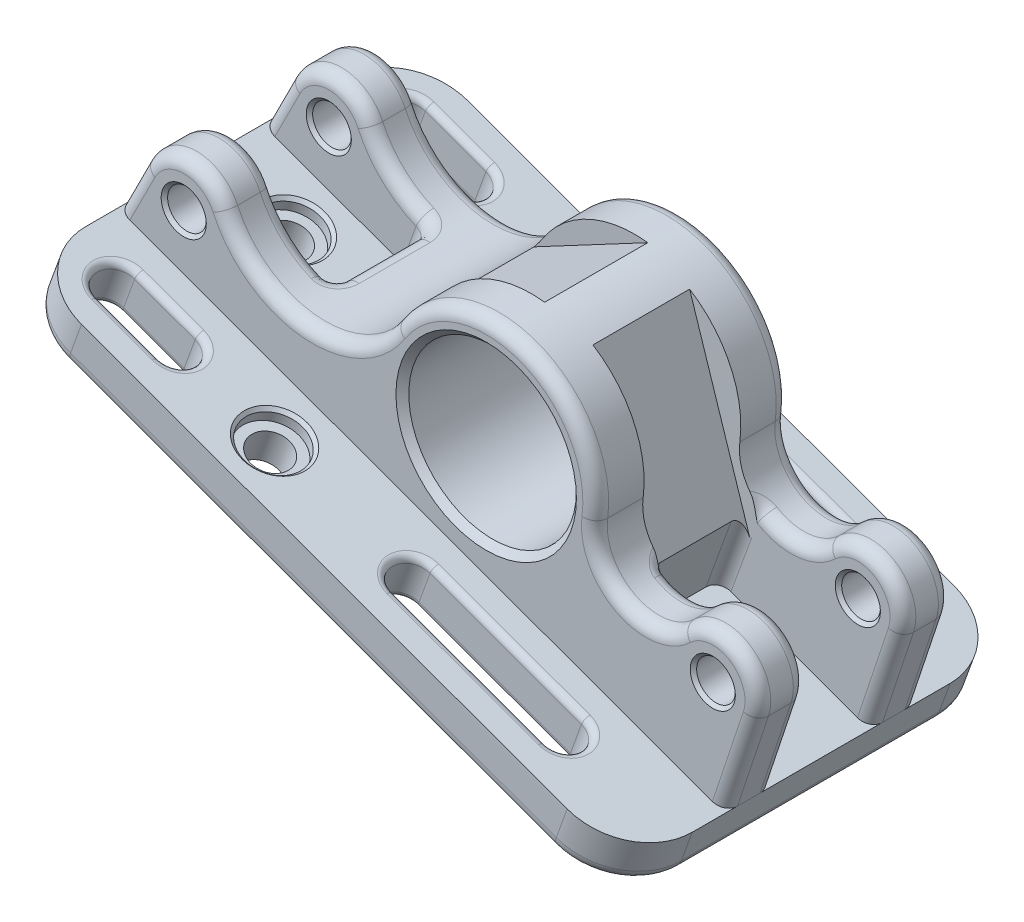
SolidWorks part; units mm, degrees
material "7075-T6, Plate (SS)"
ref_plane "Front Plane" through (0, 0, 0) normal (0, 0, 1) x (1, 0, 0)
ref_plane "Top Plane" through (0, 0, 0) normal (0, 1, 0) x (1, 0, 0)
ref_plane "Right Plane" through (0, 0, 0) normal (1, 0, 0) x (0, 0, -1)
sketch "Sketch1" plane through (0, 0, 0) normal (0, 0, 1) x (1, 0, 0)
  line L1 (2.9256, 48.9181) -> (97.0713, 14.6519)
  line L2 (97.0713, 14.6519) -> (109.144, 47.8213) construction
  line L3 (2.9256, 48.9181) -> (16.6344, 86.5828) construction
  line L4 (64.2, 56.8) -> (64.2, 145) construction
  line L5 (17.2835, 64.9758) -> (54.2, 106.8)
  line L6 (74.2, 121.8) -> (101.5245, 50.2773)
  line L7 (40.7, 148) -> (40.7, 52.5253) construction
  line L8 (87.7, 148) -> (87.7, 56.8) construction
  arc A1 (97.0713, 14.6519) -> (108.8436, 11.9213) centre (114.1723, 61.6365) ccw
  circle A2 centre (17.2835, 64.9758) radius 3
  circle A3 centre (101.5245, 50.2773) radius 3
  circle A8 centre (74.2, 121.8) radius 3
  circle A9 centre (54.2, 106.8) radius 3
  spline S1 degree 3 poles (108.8436, 11.9213) (110.0019, 11.7972) (111.159, 11.6604) (114.5227, 11.2279) (116.7249, 10.9021) (123.3121, 9.8294) (127.6782, 8.9871) (140.7169, 6.3137) (149.3307, 4.3374) (166.474, 1.206) (175.0008, 0.0515) (187.7816, -0.2014) (192.0406, -0.0398) (200.5758, 0.9156) (204.8521, 1.7093) (209.1515, 2.8921) knots 0.514918 0.514918 0.514918 0.514918 0.53125 0.53125 0.5625 0.5625 0.625 0.625 0.75 0.75 0.875 0.875 0.9375 0.9375 1 1 1 1
  point P0 (64.2, 56.8)
  point P18 (17.2835, 64.9758)
  point P19 (101.5245, 50.2773)
  point P26 (74.2, 121.8)
  point P27 (54.2, 106.8)
  dimension "D11" = 6
  dimension "D12" = 6
  dimension "D15" = 46.9165
  dimension "D17" = 6
  dimension "D18" = 6
  dimension "D3" = 20
  dimension "D4" = 35
  dimension "D5" = 8
  dimension "D6" = 10
  dimension "D7" = 8
  dimension "D8" = 10
  dimension "D9" = 65
  dimension "D10" = 50
  dimension "D13" = 37.3245
  dimension "D14" = 6.5227
  dimension "D16" = 8.1758
sketch "Sketch4" plane through (0, 0, 0) normal (0, 0, 1) x (1, 0, 0)
  line L0 (7.0298, 60.1945) -> (4.6357, 53.6166)
  line L1 (4.6357, 53.6166) -> (98.7814, 19.3504)
  line L2 (7.0298, 60.1945) -> (101.1755, 25.9282)
  line L3 (2.9256, 48.9181) -> (16.6344, 86.5828) construction
  line L4 (97.0713, 14.6519) -> (109.144, 47.8213) construction
  line L5 (101.1755, 25.9282) -> (98.7814, 19.3504)
  dimension "D1" = 7
extrude "Boss-Extrude2" add sketch "Sketch4" along normal blind 30 and the other way blind 30 separate body
sketch "Sketch5" plane through (0, 0, 0) normal (0, 0, 1) x (1, 0, 0)
  line L0 (101.1755, 25.9282) -> (105.9964, 40.4548)
  line L1 (7.0298, 60.1945) -> (11.0338, 68.1294)
  line L5 (101.1755, 25.9282) -> (7.0298, 60.1945)
  line L8 (17.2835, 64.9758) -> (6.1272, 34.324) construction
  line L10 (101.1755, 25.9282) -> (7.0298, 60.1945) construction
  line L12 (7.0298, 60.1945) -> (4.6357, 53.6166) construction
  arc A0 (81.0509, 54.5531) -> (49.9057, 66.0017) centre (64.2, 56.8) ccw
  arc A1 (105.9964, 40.4548) -> (94.5124, 47.7165) centre (99.3527, 42.6596) ccw
  arc A2 (23.6504, 67.8857) -> (11.0338, 68.1294) centre (17.2835, 64.9758) ccw
  circle A3 centre (64.2, 56.8) radius 13
  circle A4 centre (99.3527, 42.6596) radius 3
  circle A5 centre (17.2835, 64.9758) radius 3
  arc A6 (23.6504, 67.8857) -> (49.9057, 66.0017) centre (37.293, 74.1209) ccw
  arc A7 (81.0509, 54.5531) -> (94.5124, 47.7165) centre (88.9807, 53.4957) ccw
  point P18 (16.5995, 63.0965)
  point P22 (17.2835, 64.9758)
  dimension "D1" = 14.0006
  dimension "D2" = 4
  dimension "D3" = 14
  dimension "D8" = 26
  dimension "D9" = 6
  dimension "D5" = 6
  dimension "D6" = 2
extrude "Boss-Extrude5" add sketch "Sketch5" along normal blind 15 and the other way blind 15 contours L5 A3 A4 A5 region at (54.4798, 44.0974, 0)
sketch "Sketch6" plane through (20.1685, 55.4124, 0) normal (0.342, 0.9397, 0) x (0.9397, -0.342, 0)
  line L1 (-13.9818, -7.5) -> (10.9889, -7.5)
  line L2 (61.3272, -7.5) -> (95.1205, -7.5)
  line L3 (-13.9818, 7.5) -> (10.9889, 7.5)
  line L4 (95.1205, -7.5) -> (95.1205, 7.5)
  line L6 (-13.9818, 30) -> (-13.9818, -30) construction
  line L7 (61.3272, 7.5) -> (61.3272, -7.5)
  line L8 (10.9889, 7.5) -> (10.9889, -7.5)
  line L9 (-13.9818, 7.5) -> (-13.9818, -7.5)
  line L10 (61.3272, 7.5) -> (95.1205, 7.5)
  point P0 (0, 0)
  dimension "D1" = 15
extrude "Cut-Extrude1" cut sketch "Sketch6" along normal blind 41
chamfer "Chamfer1" distance 1 angle 45 2 edges at (77.2, 56.8, -15) (77.2, 56.8, 15)
sketch "Sketch8" plane through (20.1685, 55.4124, 0) normal (0.342, 0.9397, 0) x (0.9397, -0.342, 0)
  line L0 (40.9015, 0) -> (-1.0985, 0) construction
  line L1 (19.9015, 0) -> (19.9015, 22.5) construction
  line L2 (27.9015, -14) -> (53.9015, -14) construction
  line L3 (27.9015, -14) -> (53.9015, -14)
  line L4 (40.9015, -14) -> (40.9015, 14) construction
  circle A0 centre (-1.0985, 0) radius 3
  circle A1 centre (19.9015, 22.5) radius 3
  circle A2 centre (19.9015, -22.5) radius 3
  dimension "D2" = 6
  dimension "D3" = 6
  dimension "D4" = 6
  dimension "D1" = 42
  dimension "D5" = 22.5
extrude "Cut-Extrude3" cut sketch "Sketch8" against normal blind 10 contours A2 | A0 | A1 region at (19.1362, 55.7881, 0) region at (38.8698, 48.6057, -22.5) region at (38.8698, 48.6057, 22.5)
chamfer "Chamfer3" distance 0.5 angle 45 8 edges at (102.3527, 42.6596, -7.5) (102.3527, 42.6596, -15) (96.3527, 42.6596, 7.5) (102.3527, 42.6596, 15) (14.2835, 64.9758, 7.5) (20.2835, 64.9758, 15) (20.2835, 64.9758, -7.5) (20.2835, 64.9758, -15)
sketch "Sketch9" plane through (20.1685, 55.4124, 0) normal (0.342, 0.9397, 0) x (0.9397, -0.342, 0)
  circle A0 centre (19.9015, -22.5) radius 3 construction
  circle A1 centre (-1.0985, 0) radius 3 construction
  circle A2 centre (19.9015, 22.5) radius 3 construction
  circle A3 centre (19.9015, -22.5) radius 3
  circle A4 centre (-1.0985, 0) radius 3
  circle A5 centre (19.9015, 22.5) radius 3
  circle A6 centre (19.9015, -22.5) radius 4.5
  circle A7 centre (-1.0985, 0) radius 4.5
  circle A8 centre (19.9015, 22.5) radius 4.5
  dimension "D1" = 1.5
extrude "Cut-Extrude4" cut sketch "Sketch9" against normal blind 2
chamfer "Chamfer5" distance 0.5 angle 45 1 edges at (34.6412, 50.1448, 22.5)
chamfer "Chamfer6" distance 0.5 angle 45 2 edges at (14.9076, 57.3272, 0) (34.6412, 50.1448, -22.5)
sketch "Sketch10" plane through (20.1685, 55.4124, 0) normal (0.342, 0.9397, 0) x (0.9397, -0.342, 0)
  line L0 (-13.9818, 22.5) -> (86.2059, 22.5) construction
  line L1 (86.2059, 30) -> (86.2059, 15) construction
  line L2 (42.7393, 25.5) -> (42.7393, 19.5) construction
  line L3 (42.7393, 19.5) -> (67.7393, 19.5)
  line L4 (67.7393, 25.5) -> (67.7393, 19.5) construction
  line L5 (42.7393, 25.5) -> (67.7393, 25.5)
  line L7 (42.7393, 19.5) -> (67.7393, 25.5) construction
  line L8 (42.7393, 25.5) -> (67.7393, 19.5) construction
  line L9 (-5.974, 25.552) -> (-5.974, 19.552) construction
  line L10 (-5.974, 19.552) -> (4.026, 19.552)
  line L11 (4.026, 25.552) -> (4.026, 19.552) construction
  line L12 (-5.974, 25.552) -> (4.026, 25.552)
  line L13 (-5.974, 19.552) -> (4.026, 25.552) construction
  line L14 (-5.974, 25.552) -> (4.026, 19.552) construction
  line L15 (-1.0985, 0) -> (63.2348, 0) construction
  line L16 (-5.974, -25.552) -> (4.026, -19.552) construction
  line L17 (-5.974, -19.552) -> (4.026, -25.552) construction
  line L18 (4.026, -25.552) -> (4.026, -19.552) construction
  line L19 (-5.974, -25.552) -> (-5.974, -19.552) construction
  line L20 (42.7393, -25.5) -> (67.7393, -19.5) construction
  line L21 (42.7393, -19.5) -> (67.7393, -25.5) construction
  line L22 (67.7393, -25.5) -> (67.7393, -19.5) construction
  line L23 (42.7393, -25.5) -> (42.7393, -19.5) construction
  line L24 (-5.974, -25.552) -> (4.026, -25.552)
  line L25 (-5.974, -19.552) -> (4.026, -19.552)
  line L26 (42.7393, -25.5) -> (67.7393, -25.5)
  line L27 (42.7393, -19.5) -> (67.7393, -19.5)
  arc A0 (42.7393, 25.5) -> (42.7393, 19.5) centre (42.7393, 22.5) ccw
  arc A1 (67.7393, 25.5) -> (67.7393, 19.5) centre (67.7393, 22.5) cw
  arc A3 (-5.974, 25.552) -> (-5.974, 19.552) centre (-5.974, 22.552) ccw
  arc A4 (4.026, 25.552) -> (4.026, 19.552) centre (4.026, 22.552) cw
  arc A5 (4.026, -25.552) -> (4.026, -19.552) centre (4.026, -22.552) ccw
  arc A6 (-5.974, -25.552) -> (-5.974, -19.552) centre (-5.974, -22.552) cw
  arc A7 (67.7393, -25.5) -> (67.7393, -19.5) centre (67.7393, -22.5) ccw
  arc A8 (42.7393, -25.5) -> (42.7393, -19.5) centre (42.7393, -22.5) cw
  point P5 (55.2393, 22.5)
  point P11 (-0.974, 22.552)
  point P20 (19.9015, 22.5)
  point P36 (19.9015, -22.5)
  point P37 (-0.974, -22.552)
  point P38 (55.2393, -22.5)
  dimension "D2" = 3
  dimension "D3" = 3
  dimension "D1" = 6
  dimension "D4" = 25
  dimension "D5" = 6
  dimension "D6" = 10
extrude "Cut-Extrude5" cut sketch "Sketch10" against normal through all
fillet "Fillet5" radius 10 4 edges at (99.9785, 22.6393, -30) (99.9785, 22.6393, 30) (5.8328, 56.9055, 30) (5.8328, 56.9055, -30)
sketch "Sketch11" plane through (0, 0, -7.5) normal (0, 0, 1) x (1, 0, 0)
  line L0 (82.1122, 36.0592) -> (97.973, 30.2864)
  line L1 (77.7972, 34.4372) -> (101.1755, 25.9282)
  line L2 (82.1122, 36.0592) -> (83.8223, 40.7577)
  line L3 (97.973, 30.2864) -> (99.6831, 34.9849)
  line L4 (99.6831, 34.9849) -> (83.8223, 40.7577)
  line L5 (82.9672, 38.4085) -> (23.1794, 60.1695) construction
  circle A0 centre (44.4398, 52.4313) radius 4
  dimension "D7" = 8
  dimension "D1" = 3
  dimension "D2" = 5
  dimension "D3" = 4.5
  dimension "D4" = 90
  dimension "D5" = 3.5
  dimension "D6" = 16.8787
  dimension "D8" = 41
sketch "Sketch12" plane through (81.0071, -29.4842, 0) normal (0.9397, -0.342, 0) x (0, 0, -1)
  line L0 (-7.5, 58.9686) -> (7.5, 58.9686)
  line L1 (-7.5, 58.9686) -> (-7.5, 127.5267)
  line L2 (7.5, 58.9686) -> (7.5, 127.5267)
  line L3 (-7.5, 127.5267) -> (7.5, 127.5267)
fillet "Fillet9" radius 2 8 edges at (96.0291, 20.3521, -27.0711) (51.7085, 36.4835, -30) (7.388, 52.6149, -27.0711) (4.6357, 53.6166, 0) (7.388, 52.6149, 27.0711) (51.7085, 36.4835, 30) (96.0291, 20.3521, 27.0711) (98.7814, 19.3504, 0)
fillet "Fillet10" radius 1 32 edges at (84.2476, 24.6403, -22.5) (69.6823, 29.9416, -25.5) (55.1171, 35.2429, -22.5) (84.2476, 24.6403, 22.5) (69.6823, 29.9416, 19.5) (55.1171, 35.2429, 22.5) (16.859, 49.1677, -19.552) (24.3766, 46.4315, -22.552) (16.859, 49.1677, -25.552) (16.859, 49.1677, 25.552) (24.3766, 46.4315, 22.552) (16.859, 49.1677, 19.552) (86.6417, 31.2181, 22.5) (72.0765, 36.5194, 25.5) (57.5112, 41.8207, 22.5) (26.7707, 53.0094, 22.552) (19.2532, 55.7455, 25.552) (11.7356, 58.4817, 22.552) (86.6417, 31.2181, -22.5) (72.0765, 36.5194, -19.5) (57.5112, 41.8207, -22.5) (26.7707, 53.0094, -22.552) (19.2532, 55.7455, -19.552) (11.7356, 58.4817, -22.552) (69.6823, 29.9416, -19.5) (69.6823, 29.9416, 25.5) (9.3415, 51.9038, -22.552) (9.3415, 51.9038, 22.552) (72.0765, 36.5194, 19.5) (19.2532, 55.7455, 19.552) (72.0765, 36.5194, -25.5) (19.2532, 55.7455, -25.552)
fillet "Fillet11" radius 2 14 edges at (103.586, 33.1915, -15) (103.0939, 48.5761, -15) (85.3582, 46.3628, -15) (9.0318, 64.162, -15) (17.4187, 71.9748, -15) (36.2194, 59.1594, -15) (103.586, 33.1915, 15) (103.0939, 48.5761, 15) (85.3582, 46.3628, 15) (9.0318, 64.162, 15) (17.4187, 71.9748, 15) (36.2194, 59.1594, 15) (70.0653, 72.7561, -15) (70.0653, 72.7561, 15)
fillet "Fillet12" radius 2 4 edges at (31.9471, 55.6445, 7.5) (31.9471, 55.6445, -7.5) (80.3282, 41.3912, -7.5) (80.3282, 41.3912, 7.5)
fillet "Fillet13" radius 2 18 edges at (103.586, 33.1915, -7.5) (103.0939, 48.5761, -7.5) (103.586, 33.1915, 7.5) (103.0939, 48.5761, 7.5) (89.6319, 45.5222, 7.5) (83.413, 47.751, 7.0397) (82.8593, 48.3451, 0) (83.1292, 48.0404, -6.6416) (9.0318, 64.162, -7.5) (9.0318, 64.162, 7.5) (17.4187, 71.9748, 7.5) (26.861, 63.3425, 7.5) (32.9787, 59.7548, 6.7471) (33.3996, 59.6351, 0) (32.6711, 59.8508, -7.0678) (26.861, 63.3425, -7.5) (89.6319, 45.5222, -7.5) (17.4187, 71.9748, -7.5)
sketch "Sketch13" plane through (0, 0, 0) normal (0, 0, 1) x (1, 0, 0)
  line L0 (99.3527, 42.6596) -> (99.3527, 93.8474) construction
  line L1 (99.3527, 42.6596) -> (82.1577, 95.5806) construction
  line L2 (97.8077, 47.4149) -> (82.5908, 42.4707)
  line L3 (97.8077, 47.4149) -> (85.447, 85.4572)
  line L4 (82.5908, 42.4707) -> (70.2301, 80.5129)
  line L5 (85.447, 85.4572) -> (70.2301, 80.5129)
  dimension "D1" = 18
  dimension "D2" = 5
  dimension "D3" = 16
  dimension "D4" = 40
extrude "Cut-Extrude6" cut sketch "Sketch13" against normal blind 7.5 and the other way blind 7.5
sketch "Sketch14" plane through (0, 0, 0) normal (0, 0, 1) x (1, 0, 0)
  line L0 (18.9652, 55.3182) -> (36.8862, 104.5556) construction
  line L1 (14.7366, 56.8573) -> (23.1938, 53.7792) construction
  line L2 (18.9652, 55.3182) -> (86.1932, 91.064) construction
  line L3 (43.7311, 68.4865) -> (46.548, 63.1888)
  line L4 (43.7311, 68.4865) -> (70.2196, 82.5707)
  line L5 (46.548, 63.1888) -> (73.0364, 77.273)
  line L6 (70.2196, 82.5707) -> (73.0364, 77.273)
  point P4 (17.2835, 64.9758)
  dimension "D1" = 42
  dimension "D2" = 6
  dimension "D3" = 25
  dimension "D4" = 30
extrude "Cut-Extrude7" cut sketch "Sketch14" against normal blind 8 and the other way blind 8
